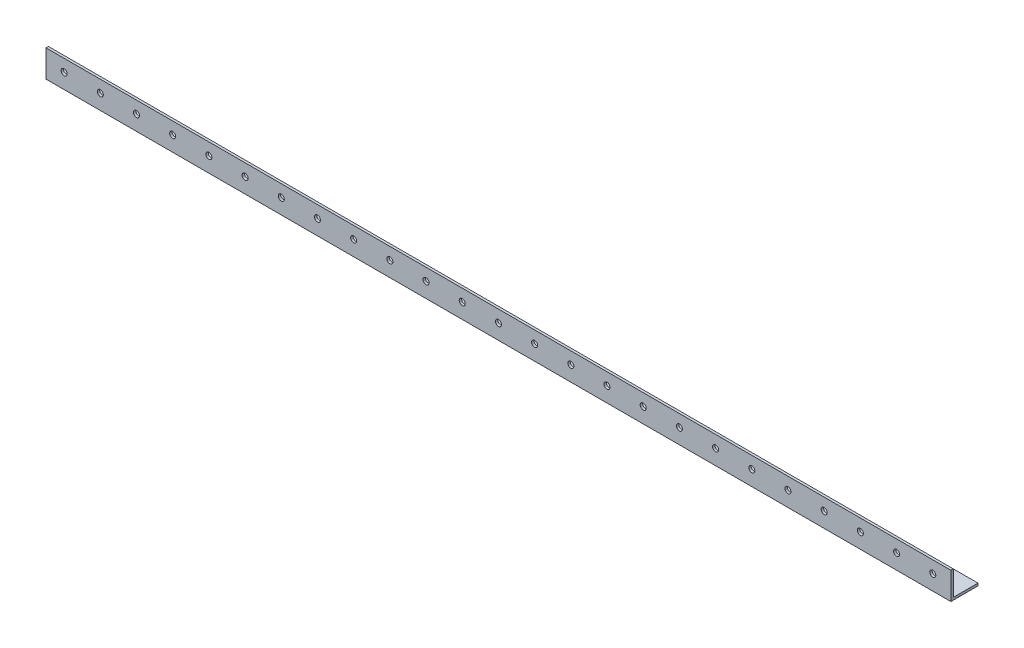
SolidWorks part; units mm, degrees
ref_plane "Спереди" through (0, 0, 0) normal (0, 0, 1) x (1, 0, 0)
ref_plane "Сверху" through (0, 0, 0) normal (0, 1, 0) x (1, 0, 0)
ref_plane "Справа" through (0, 0, 0) normal (1, 0, 0) x (0, 0, -1)
sketch "Эскиз1" plane through (0, 0, 0) normal (1, 0, 0) x (0, 0, -1)
  line L0 (0, 0) -> (0, 45)
  line L1 (0, 0) -> (45, 0)
  dimension "D1" = 45
  dimension "D2" = 45
extrude "Вытянуть-Тонкостенный1" add sketch "Эскиз1" along normal blind 1500 thin thin type one direction reverse wall 4
sketch "Эскиз2" plane through (0, 0, 0) normal (0, 0, 1) x (1, 0, 0)
  circle A0 centre (30, 25) radius 5
  circle A1 centre (90, 25) radius 5
  circle A2 centre (150, 25) radius 5
  circle A3 centre (210, 25) radius 5
  circle A8 centre (270, 25) radius 5
  circle A9 centre (330, 25) radius 5
  circle A10 centre (390, 25) radius 5
  circle A11 centre (450, 25) radius 5
  circle A12 centre (510, 25) radius 5
  circle A13 centre (570, 25) radius 5
  circle A14 centre (630, 25) radius 5
  circle A15 centre (690, 25) radius 5
  circle A16 centre (750, 25) radius 5
  circle A17 centre (810, 25) radius 5
  circle A18 centre (870, 25) radius 5
  circle A19 centre (930, 25) radius 5
  circle A20 centre (990, 25) radius 5
  circle A21 centre (1050, 25) radius 5
  circle A22 centre (1110, 25) radius 5
  circle A23 centre (1170, 25) radius 5
  circle A24 centre (1230, 25) radius 5
  circle A25 centre (1290, 25) radius 5
  circle A26 centre (1350, 25) radius 5
  circle A27 centre (1410, 25) radius 5
  circle A28 centre (1470, 25) radius 5
  dimension "D1" = 25
extrude "Вырез-Вытянуть1" cut sketch "Эскиз2" against normal through all
sketch "Эскиз3" plane through (0, 0, 0) normal (0, -1, 0) x (1, 0, 0)
  circle A0 centre (30, -25) radius 5
  circle A1 centre (90, -25) radius 5
  circle A2 centre (150, -25) radius 5
  circle A3 centre (210, -25) radius 5
  circle A4 centre (270, -25) radius 5
  circle A5 centre (330, -25) radius 5
  circle A6 centre (390, -25) radius 5
  circle A7 centre (450, -25) radius 5
  circle A8 centre (510, -25) radius 5
  circle A9 centre (570, -25) radius 5
  circle A10 centre (630, -25) radius 5
  circle A11 centre (690, -25) radius 5
  circle A12 centre (750, -25) radius 5
  circle A13 centre (810, -25) radius 5
  circle A14 centre (870, -25) radius 5
  circle A15 centre (930, -25) radius 5
  circle A16 centre (990, -25) radius 5
  circle A17 centre (1050, -25) radius 5
  circle A18 centre (1110, -25) radius 5
  circle A19 centre (1170, -25) radius 5
  circle A20 centre (1230, -25) radius 5
  circle A21 centre (1290, -25) radius 5
  circle A22 centre (1350, -25) radius 5
  circle A23 centre (1410, -25) radius 5
  circle A24 centre (1470, -25) radius 5
  dimension "D1" = 25
extrude "Вырез-Вытянуть2" cut sketch "Эскиз3" against normal through all
